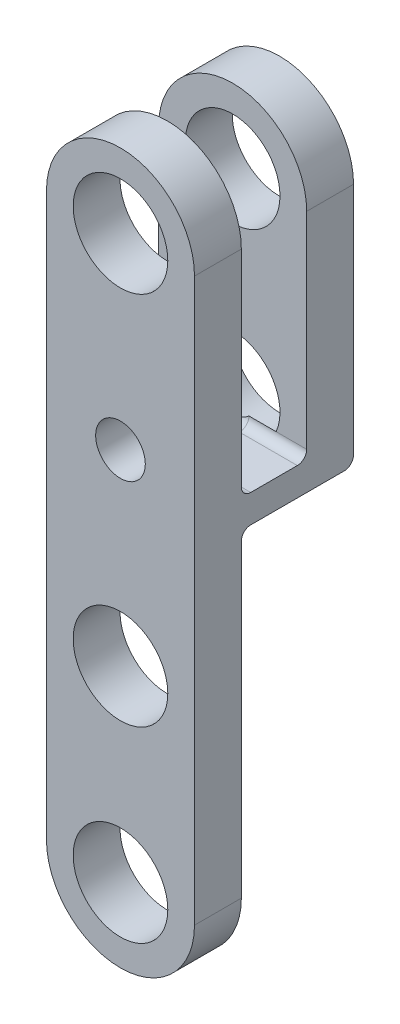
SolidWorks part; units mm, degrees
material "ABS"
ref_plane "Plan de face" through (0, 0, 0) normal (0, 0, 1) x (1, 0, 0)
ref_plane "Plan de dessus" through (0, 0, 0) normal (0, 1, 0) x (1, 0, 0)
ref_plane "Plan de droite" through (0, 0, 0) normal (1, 0, 0) x (0, 0, -1)
sketch "Esquisse1" plane through (0, 0, 0) normal (0, 0, 1) x (1, 0, 0)
  line L0 (0, 0) -> (0, -76.2) construction
  line L1 (-10.033, 0) -> (-10.033, -76.2)
  line L2 (10.033, 0) -> (10.033, -76.2)
  circle A0 centre (0, 0) radius 6.4135
  arc A1 (10.033, 0) -> (-10.033, 0) centre (0, 0) ccw
  arc A2 (-10.033, -76.2) -> (10.033, -76.2) centre (0, -76.2) ccw
  circle A3 centre (0, -76.2) radius 6.4135
  circle A7 centre (0, -25.4) radius 3.3655
  circle A8 centre (0, -50.8) radius 6.4135
  dimension "D4" = 12.827
  dimension "D5" = 6.731
  dimension "D1" = 25.4
  dimension "D2" = 25.4
  dimension "D3" = 76.2
extrude "Boss.-Extru.1" add sketch "Esquisse1" along normal blind 6.35
sketch "Esquisse2" plane through (0, 0, 0) normal (0, 0, -1) x (-1, 0, 0)
  line L0 (-10.033, -76.2) -> (-10.033, 0) construction
  line L1 (-10.033, -33.02) -> (10.033, -33.02)
  line L2 (-10.033, -33.02) -> (-10.033, -29.21)
  line L3 (-10.033, -29.21) -> (10.033, -29.21)
  line L4 (10.033, -33.02) -> (10.033, -29.21)
  line L5 (10.033, 0) -> (10.033, -76.2) construction
  circle A1 centre (0, -25.4) radius 3.3655 construction
  dimension "D1" = 3.81
  dimension "D2" = 3.81
extrude "Boss.-Extru.2" add sketch "Esquisse2" along normal blind 8.8582
ref_plane "Plan1" through (0, 0, -4.4291) normal (0, 0, 1) x (1, 0, 0)
mirror "Symétrie1" about plane through (0, 0, -4.4291) normal (0, 0, 1) of "Boss.-Extru.1"
sketch "Esquisse3" plane through (0, 0, -15.2082) normal (0, 0, -1) x (-1, 0, 0)
  line L0 (-10.033, -76.2) -> (-10.033, 0) construction
  line L1 (-10.033, -33.02) -> (16.3006, -33.02)
  line L2 (-10.033, -33.02) -> (-10.033, -94.8058)
  line L3 (-10.033, -94.8058) -> (16.3006, -94.8058)
  line L4 (16.3006, -33.02) -> (16.3006, -94.8058)
  line L5 (-10.033, -33.02) -> (10.033, -33.02) construction
extrude "Enlèv. mat.-Extru.1" cut sketch "Esquisse3" against normal up to next
fillet "Congé1" radius 1.27 4 edges at (0, -29.21, 0) (0, -29.21, -8.8582) (0, -33.02, 0) (0, -33.02, -15.2082)
sketch "Esquisse4" plane through (0, 0, -15.2082) normal (0, 0, -1) x (-1, 0, 0)
  circle A0 centre (0, -25.4) radius 6.4135
  dimension "D1" = 12.827
extrude "Enlèv. mat.-Extru.2" cut sketch "Esquisse4" against normal up to surface (6.35 mm away) up to face at (6.4135, 0, -8.8582)
